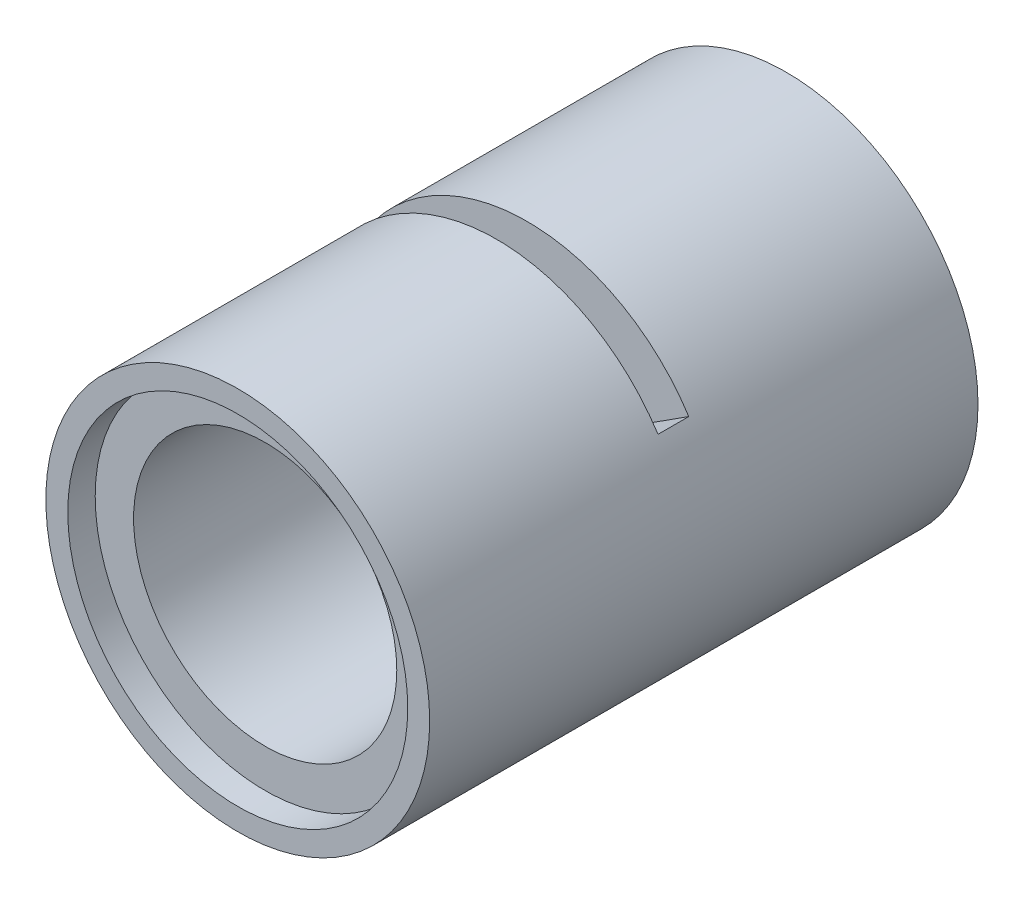
SolidWorks part; units mm, degrees
ref_plane "Front Plane" through (0, 0, 0) normal (0, 0, 1) x (1, 0, 0)
ref_plane "Top Plane" through (0, 0, 0) normal (0, 1, 0) x (1, 0, 0)
ref_plane "Right Plane" through (0, 0, 0) normal (1, 0, 0) x (0, 0, -1)
sketch "Sketch1" plane through (0, 0, 0) normal (0, 0, 1) x (1, 0, 0)
  circle A0 centre (0, 0) radius 3.5
  dimension "D1" = 7
extrude "Boss-Extrude1" add sketch "Sketch1" along normal blind 10
sketch "Sketch3" plane through (0, 0, 10) normal (0, 0, 1) x (1, 0, 0)
  circle A0 centre (0, 0) radius 2.4
  dimension "D1" = 4.8
extrude "Cut-Extrude1" cut sketch "Sketch3" against normal through all
sketch "Sketch4" plane through (0, 0, 10) normal (0, 0, 1) x (1, 0, 0)
  circle A0 centre (0, 0) radius 3.1
  dimension "D1" = 6.2
extrude "Cut-Extrude2" cut sketch "Sketch4" against normal blind 0.5
ref_plane "Plane1" through (0, 0, 5) normal (0, 0, 1) x (1, 0, 0)
mirror "Mirror1" about plane through (0, 0, 5) normal (0, 0, 1) of "Cut-Extrude2"
ref_axis "Axis1" through (0, 0, -0.5) along (0, 0, 1)
ref_plane "Curve Sketch" through (0, 4, 0) normal (0, 1, 0) x (1, 0, 0)
sketch "Sketch43" plane through (0, 4, 0) normal (0, 1, 0) x (1, 0, 0)
  line L0 (0, 0) -> (0, -10) construction
  line L1 (-3.5, -10) -> (3.5, -10) construction
  line L3 (-3.5, -4.7197) -> (3.5, -4.7197)
  line L4 (-3.5, -4.7197) -> (-3.5, -5.2803)
  line L5 (-3.5, -5.2803) -> (3.5, -5.2803)
  line L6 (3.5, -4.7197) -> (3.5, -5.2803)
  line L7 (-3.5, -4.7197) -> (3.5, -5.2803) construction
  line L8 (-3.5, -5.2803) -> (3.5, -4.7197) construction
  point P5 (0, -5)
  dimension "D1" = 7
wrap "Wrap1" sketch "Sketch43" wrap type deboss source sketch "Sketch43" thickness 1 face at (3.5, 0, 10) parameters "D1"=1
